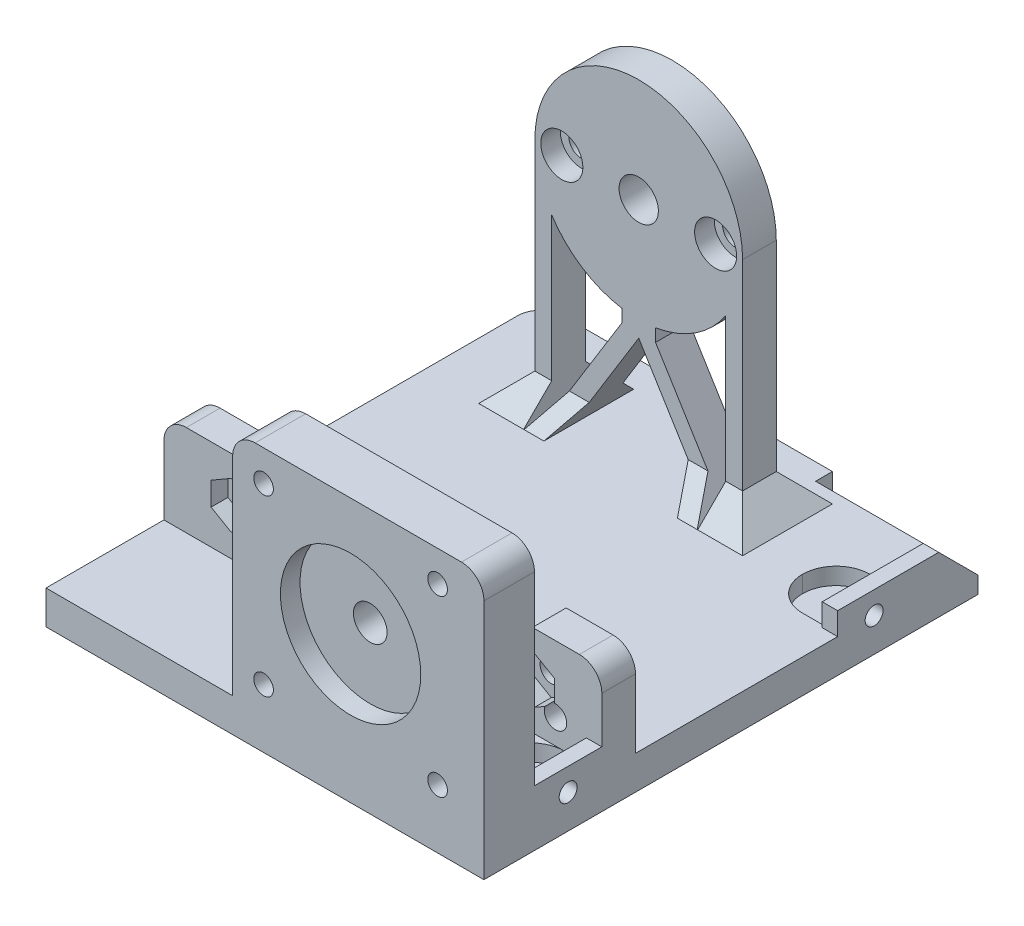
SolidWorks part; units mm, degrees
ref_plane "Front Plane" through (0, 0, 0) normal (0, 0, 1) x (1, 0, 0)
ref_plane "Top Plane" through (0, 0, 0) normal (0, 1, 0) x (1, 0, 0)
ref_plane "Right Plane" through (0, 0, 0) normal (1, 0, 0) x (0, 0, -1)
sketch "Sketch1" plane through (0, 0, 0) normal (0, 0, 1) x (1, 0, 0)
  circle A0 centre (0, 0) radius 3.5
  circle A1 centre (-13.7, 0) radius 2.25
  circle A2 centre (13.7, 0) radius 2.25
  circle A3 centre (0, 0) radius 18.5
  dimension "D3" = 4.5
  dimension "D4" = 7
  dimension "D5" = 37
  dimension "D1" = 13.7
  dimension "D2" = 13.7
extrude "Boss-Extrude1" add sketch "Sketch1" along normal blind 6
sketch "Sketch3" plane through (0, 0, 6) normal (0, 0, 1) x (1, 0, 0)
  line L0 (-18.5, 0) -> (-18.5, -46.68)
  line L1 (18.5, 0) -> (18.5, -46.68)
  line L2 (18.5, -46.68) -> (-18.5, -46.68)
  line L3 (15.5, 0) -> (15.5, -43.68)
  line L4 (15.5, -43.68) -> (-15.5, -43.68)
  line L5 (-15.5, 0) -> (-15.5, -43.68)
  line L6 (-15.5, -43.68) -> (0, -18.5) construction
  line L7 (0, -18.5) -> (15.5, -43.68) construction
  line L8 (-15.5, -40.8186) -> (-1.7125, -18.4206)
  line L9 (0, 0) -> (0, -18.5) construction
  line L10 (0, -18.5) -> (0, -43.68) construction
  line L11 (-13.7386, -43.68) -> (0, -21.3614)
  line L12 (15.5, -40.8186) -> (1.7125, -18.4206)
  line L13 (13.7386, -43.68) -> (0, -21.3614)
  line L14 (-15.5, -10.0995) -> (-18.5, 0)
  line L15 (18.5, 0) -> (15.5, -10.0995)
  line L16 (-3, -20.5121) -> (-3, -18.2551)
  line L17 (3, -20.5121) -> (3, -18.2551)
  circle A0 centre (0, 0) radius 18.5 construction
  circle A1 centre (0, 0) radius 18.5
  circle M4 centre (0, 0) radius 18.5
  dimension "D1" = 46.68
  dimension "D3" = 1.5
  dimension "D4" = 1.5
  dimension "D5" = 3
  dimension "D2" = 3
extrude "Boss-Extrude2" add sketch "Sketch3" against normal blind 6 contours L5 L0 L2 L1 L3 L4 M4 | L13 L4 L3 L12 L8 L5 L11 M4 | L12 L17 M4 | L16 L8 M4
sketch "Sketch4" plane through (0, 0, 0) normal (0, 0, 1) x (1, 0, 0)
  line L0 (-33.57, -46.68) -> (-33.57, -40.68)
  line L1 (-18.5, -46.68) -> (44.43, -46.68)
  line L7 (-33.57, -46.68) -> (-18.5, -46.68)
  line L8 (-33.57, -40.68) -> (44.43, -40.68)
  line L9 (44.43, -40.68) -> (44.43, -46.68)
  dimension "D1" = 44.43
  dimension "D2" = 78
  dimension "D3" = 6
extrude "Boss-Extrude3" add sketch "Sketch4" along normal blind 85
ref_plane "Plane1" through (0, 0, 67) normal (0, 0, -1) x (-1, 0, 0)
sketch "Sketch6" plane through (0, 0, 67) normal (0, 0, -1) x (-1, 0, 0)
  line L0 (-44.43, -40.68) -> (33.57, -40.68) construction
  line L2 (-44.43, -46.68) -> (33.57, -46.68) construction
  line L7 (-44.43, -43.68) -> (33.57, -43.68)
  line L8 (-44.43, -43.68) -> (-44.43, -24.43)
  line L9 (-44.43, -24.43) -> (33.57, -24.43)
  line L10 (33.57, -43.68) -> (33.57, -24.43)
  line L11 (-44.43, -46.68) -> (-44.43, -40.68) construction
  circle A0 centre (-32.43, -32.43) radius 2
  circle A1 centre (21.57, -32.43) radius 2
  circle A2 centre (-20.68, -20.68) radius 12
  circle A3 centre (-36.18, -36.18) radius 2
  circle A4 centre (-5.18, -36.18) radius 2
  dimension "D2" = 4
  dimension "D3" = 4
  dimension "D10" = 24
  dimension "D15" = 4
  dimension "D4" = 12
  dimension "D5" = 66
  dimension "D6" = 12
  dimension "D7" = 8
  dimension "D8" = 23.75
  dimension "D9" = 3.75
  dimension "D11" = 3
  dimension "D12" = 11.25
  dimension "D13" = 4.5
  dimension "D14" = 8.25
  dimension "D16" = 31
extrude "Boss-Extrude5" add sketch "Sketch6" along normal blind 6 contours A2 L9 L8 L7 L10 A1 A0
sketch "Sketch5" plane through (0, 0, 85) normal (0, 0, 1) x (1, 0, 0)
  line L0 (44.43, -46.68) -> (44.43, -40.68) construction
  line L5 (44.43, -46.68) -> (-33.57, -46.68) construction
  line L8 (20.68, -20.68) -> (20.68, -5.18) construction
  line L9 (20.68, -20.68) -> (36.18, -20.68) construction
  line L10 (41.68, -43.68) -> (41.68, 0.32)
  line L11 (-0.32, -43.68) -> (-0.32, 0.32)
  line L12 (-0.32, 0.32) -> (41.68, 0.32)
  circle A0 centre (20.68, -20.68) radius 3
  circle A1 centre (36.18, -5.18) radius 1.75
  circle A2 centre (36.18, -36.18) radius 1.75
  circle A3 centre (5.18, -36.18) radius 1.75
  circle A4 centre (5.18, -5.18) radius 1.75
  dimension "D3" = 6
  dimension "D6" = 3.5
  dimension "D2" = 23
  dimension "D4" = 15.5
  dimension "D5" = 15.5
  dimension "D7" = 21
  dimension "D8" = 21
  dimension "D9" = 2.75
  dimension "D10" = 3
extrude "Boss-Extrude4" add sketch "Sketch5" against normal blind 6
sketch "Sketch8" plane through (44.43, 0, 0) normal (1, 0, 0) x (0, 0, -1)
  line L0 (0, -46.68) -> (0, -40.68) construction
  line L1 (0, -43.68) -> (-25, -43.68)
  line L2 (0, -43.68) -> (0, -36.68)
  line L3 (0, -36.68) -> (-25, -36.68)
  line L4 (-25, -43.68) -> (-25, -36.68)
  line L7 (-79, -43.68) -> (-61, -43.68)
  line L8 (-79, -43.68) -> (-79, -36.68)
  line L9 (-79, -36.68) -> (-61, -36.68)
  line L10 (-61, -43.68) -> (-61, -36.68)
  line L11 (-79, -36.68) -> (-85, -36.68)
  line L12 (-79, -36.68) -> (-79, -43.68)
  line L13 (-79, -43.68) -> (-85, -43.68)
  line L14 (-85, -36.68) -> (-85, -43.68)
  line L15 (-85, -46.68) -> (0, -46.68) construction
  line L16 (-85, -46.68) -> (-85, -40.68) construction
  line L17 (-79, -40.68) -> (-79, 0.32) construction
  line L18 (-79, 0.32) -> (-85, 0.32)
  line L19 (-79, 0.32) -> (-79, -36.68)
  line L20 (-79, -36.68) -> (-85, -36.68)
  line L21 (-85, 0.32) -> (-85, -36.68)
  dimension "D6" = 7
  dimension "D7" = 7
  dimension "D8" = 18
  dimension "D9" = 3
extrude "Boss-Extrude7" add sketch "Sketch8" against normal blind 2.75
chamfer "Chamfer2" distance 7 angle 45 1 edges at (43.055, -36.68, 0)
sketch "Sketch9" plane through (44.43, 0, 0) normal (1, 0, 0) x (0, 0, -1)
  line L2 (-85, -46.68) -> (-85, 0.32) construction
  line L3 (-61, -40.68) -> (-25, -40.68) construction
  circle A0 centre (-73, -40.68) radius 1.6
  circle A1 centre (-18.5, -40.68) radius 1.6
  dimension "D3" = 3.2
  dimension "D4" = 3.2
  dimension "D1" = 12
  dimension "D2" = 54.5
extrude "Cut-Extrude2" cut sketch "Sketch9" against normal blind 10
sketch "Sketch10" plane through (0, -40.68, 0) normal (0, 1, 0) x (1, 0, 0)
  line L0 (41.68, -3) -> (41.68, -16.9) construction
  line L1 (41.68, -12.5) -> (31.68, -12.5)
  line L2 (41.68, -12.5) -> (41.68, -24.5)
  line L3 (41.68, -24.5) -> (31.68, -24.5)
  line L4 (31.68, -12.5) -> (31.68, -24.5)
  line L5 (34.43, -18.5) -> (44.43, -18.5) construction
  line L6 (34.43, -16.9) -> (34.43, -20.1) construction
  line L7 (44.43, -7) -> (44.43, -25) construction
  line L8 (34.43, -73) -> (44.43, -73) construction
  line L9 (34.43, -74.6) -> (34.43, -71.4) construction
  line L11 (-33.57, -67) -> (41.68, -67) construction
  line L12 (41.68, -67) -> (31.68, -67)
  line L13 (41.68, -67) -> (41.68, -79)
  line L14 (41.68, -79) -> (31.68, -79)
  line L15 (31.68, -67) -> (31.68, -79)
  line L16 (44.43, -61) -> (44.43, -25) construction
  dimension "D1" = 6
  dimension "D2" = 6
  dimension "D3" = 10
  dimension "D4" = 6
  dimension "D5" = 10
  dimension "D6" = 2.75
extrude "Cut-Extrude3" cut sketch "Sketch10" against normal blind 3
fillet "Fillet1" radius 6 4 edges at (31.68, -42.18, 67) (31.68, -42.18, 79) (31.68, -42.18, 24.5) (31.68, -42.18, 12.5)
sketch "Sketch11" plane through (0, 0, 6) normal (0, 0, 1) x (1, 0, 0)
  line L0 (-18.5, 0) -> (-18.5, -40.68)
  line L1 (-18.5, -40.68) -> (-11.8919, -40.68)
  line L2 (-11.8919, -40.68) -> (0, -21.3614)
  line L3 (0, -21.3614) -> (11.8919, -40.68)
  line L4 (11.8919, -40.68) -> (18.5, -40.68)
  line L5 (18.5, -40.68) -> (18.5, 0)
  line L6 (-3, -18.2551) -> (-3, -20.5121)
  line L7 (-3, -20.5121) -> (-15.4147, -40.68)
  line L8 (-15.5, -10.0995) -> (-15.5, -40.68)
  line L9 (15.5, -10.0995) -> (15.5, -40.68)
  line L10 (15.4147, -40.68) -> (3, -20.5121)
  line L11 (3, -20.5121) -> (3, -18.2551)
  circle A0 centre (0, 0) radius 18.5
  circle A1 centre (-13.7, 0) radius 2.25
  circle A2 centre (0, 0) radius 3.5
  circle A3 centre (13.7, 0) radius 2.25
  dimension "D1" = 4.5
  dimension "D2" = 7
extrude "Boss-Extrude8" add sketch "Sketch11" along normal blind 10
sketch "Sketch13" plane through (0, 0, 0) normal (0, 0, -1) x (-1, 0, 0)
  line L0 (-18.5, 0) -> (-18.5, -40.68)
  line L1 (-18.5, -40.68) -> (-11.8919, -40.68)
  line L2 (-11.8919, -40.68) -> (0, -21.3614)
  line L3 (0, -21.3614) -> (11.8919, -40.68)
  line L4 (11.8919, -40.68) -> (18.5, -40.68)
  line L5 (18.5, -40.68) -> (18.5, 0)
  line L6 (15.5, -10.0995) -> (15.5, -40.68)
  line L7 (15.4147, -40.68) -> (3, -20.5121)
  line L8 (3, -20.5121) -> (3, -18.2551)
  line L9 (-3, -18.2551) -> (-3, -20.5121)
  line L10 (-3, -20.5121) -> (-15.4147, -40.68)
  line L11 (-15.5, -40.68) -> (-15.5, -10.0995)
  circle A0 centre (0, 0) radius 18.5
  line M2 (15.5, -10.0995) -> (15.5, -40.68)
  line M4 (15.4147, -40.68) -> (3, -20.5121)
  line M5 (3, -20.5121) -> (3, -18.2551)
  arc M6 (3, -18.2551) -> (15.5, -10.0995) centre (0, 0) ccw
  line M7 (0, -21.3614) -> (11.8919, -40.68)
  line M9 (-11.8919, -40.68) -> (0, -21.3614)
  line M10 (-3, -20.5121) -> (-15.4147, -40.68)
  line M12 (-15.5, -40.68) -> (-15.5, -10.0995)
  arc M13 (-15.5, -10.0995) -> (-3, -18.2551) centre (0, 0) ccw
  line M14 (-3, -18.2551) -> (-3, -20.5121)
  line M15 (-18.5, 0) -> (-18.5, -43.68)
  line M21 (18.5, -40.68) -> (18.5, 0)
  arc M22 (18.5, 0) -> (-18.5, 0) centre (0, 0) ccw
  circle M23 centre (-13.7, 0) radius 2.25
  circle M24 centre (13.7, 0) radius 2.25
  circle M25 centre (0, 0) radius 3.5
extrude "Cut-Extrude4" cut sketch "Sketch13" against normal blind 10 contours A0 L1 L4 M14 M10 M9 M7 M4 M5 | A0 L1 M15 M12 | A0 L4 M2 M21 | A0 M22 M13 M6 M23 M25 M24
sketch "Sketch14" plane through (0, 0, 16) normal (0, 0, 1) x (1, 0, 0)
  circle A0 centre (-13.7, 0) radius 3.75
  circle A1 centre (13.7, 0) radius 3.75
  dimension "D1" = 7.5
  dimension "D2" = 7.5
extrude "Cut-Extrude5" cut sketch "Sketch14" against normal blind 3.5
chamfer "Chamfer4" distance 5 angle 45 10 edges at (13.6533, -40.68, 16) (-13.6533, -40.68, 16) (-13.6533, -40.68, 10) (-17, -40.68, 16) (-18.5, -40.68, 13) (-17, -40.68, 10) (17, -40.68, 16) (18.5, -40.68, 13) (17, -40.68, 10) (13.6533, -40.68, 10)
fillet "Fillet2" radius 4 5 edges at (-33.57, -43.68, 0) (-33.57, -24.43, 64) (44.43, -24.43, 64) (-0.32, 0.32, 82) (44.43, 0.32, 82)
sketch "Sketch15" plane through (0, 0, 67) normal (0, 0, 1) x (1, 0, 0)
  line L1 (-21.57, -28.2731) -> (-25.17, -30.3515)
  line L2 (-25.17, -30.3515) -> (-25.17, -34.5085)
  line L3 (-25.17, -34.5085) -> (-21.57, -36.5869)
  line L4 (-21.57, -36.5869) -> (-17.97, -34.5085)
  line L5 (-17.97, -34.5085) -> (-17.97, -30.3515)
  line L6 (-17.97, -30.3515) -> (-21.57, -28.2731)
  line L7 (32.43, -28.2731) -> (28.83, -30.3515)
  line L8 (28.83, -30.3515) -> (28.83, -34.5085)
  line L9 (28.83, -34.5085) -> (32.43, -36.5869)
  line L10 (32.43, -36.5869) -> (36.03, -34.5085)
  line L11 (36.03, -34.5085) -> (36.03, -30.3515)
  line L12 (36.03, -30.3515) -> (32.43, -28.2731)
  circle A0 centre (-21.57, -32.43) radius 3.6 construction
  circle A1 centre (32.43, -32.43) radius 3.6 construction
  dimension "D1" = 7.2
  dimension "D2" = 7.2
extrude "Cut-Extrude6" cut sketch "Sketch15" against normal blind 3
sketch "Sketch18" plane through (0, 0, 85) normal (0, 0, 1) x (1, 0, 0)
  line L0 (-33.57, -46.68) -> (44.43, -46.68) construction
  line L1 (44.43, 0.32) -> (-0.32, 0.32)
  line L2 (44.43, 0.32) -> (44.43, -46.68)
  line L3 (44.43, -46.68) -> (-0.32, -46.68)
  line L4 (-0.32, 0.32) -> (-0.32, -46.68)
  line L6 (-0.32, -46.68) -> (-33.57, -46.68)
  line L7 (-0.32, -46.68) -> (-0.32, -40.68)
  line L8 (-0.32, -40.68) -> (-33.57, -40.68)
  line L9 (-33.57, -46.68) -> (-33.57, -40.68)
  line M5 (44.43, -46.68) -> (44.43, -3.68)
  arc M6 (44.43, -3.68) -> (40.43, 0.32) centre (40.43, -3.68) ccw
  line M7 (40.43, 0.32) -> (3.68, 0.32)
  arc M8 (3.68, 0.32) -> (-0.32, -3.68) centre (3.68, -3.68) ccw
  line M9 (-0.32, -3.68) -> (-0.32, -40.68)
  line M10 (-0.32, -40.68) -> (-33.57, -40.68)
  line M12 (-33.57, -46.68) -> (44.43, -46.68)
  circle M13 centre (36.18, -36.18) radius 1.75
  circle M14 centre (36.18, -5.18) radius 1.75
  circle M15 centre (20.68, -20.68) radius 3
  circle M16 centre (5.18, -36.18) radius 1.75
  circle M17 centre (5.18, -5.18) radius 1.75
  line M18 (-33.57, -40.68) -> (-33.57, -46.68)
extrude "Boss-Extrude9" add sketch "Sketch18" along normal blind 3 contours L4 M9 M12 M5 M6 M7 M8 M13 M15 M17 M16 M14 | L4 M10 M18 M12
sketch "Sketch16" plane through (0, 0, 88) normal (0, 0, 1) x (1, 0, 0)
  circle A0 centre (20.68, -20.68) radius 12.5
  dimension "D1" = 25
extrude "Cut-Extrude7" cut sketch "Sketch16" against normal blind 3.5
sketch "Sketch20" plane through (0, 0, 79) normal (0, 0, -1) x (-1, 0, 0)
  circle A0 centre (-36.18, -5.18) radius 3
  circle A1 centre (-5.18, -5.18) radius 3
  circle A2 centre (-5.18, -36.18) radius 3
  circle A3 centre (-36.18, -36.18) radius 3
  dimension "D1" = 6
extrude "Cut-Extrude8" cut sketch "Sketch20" against normal blind 3
